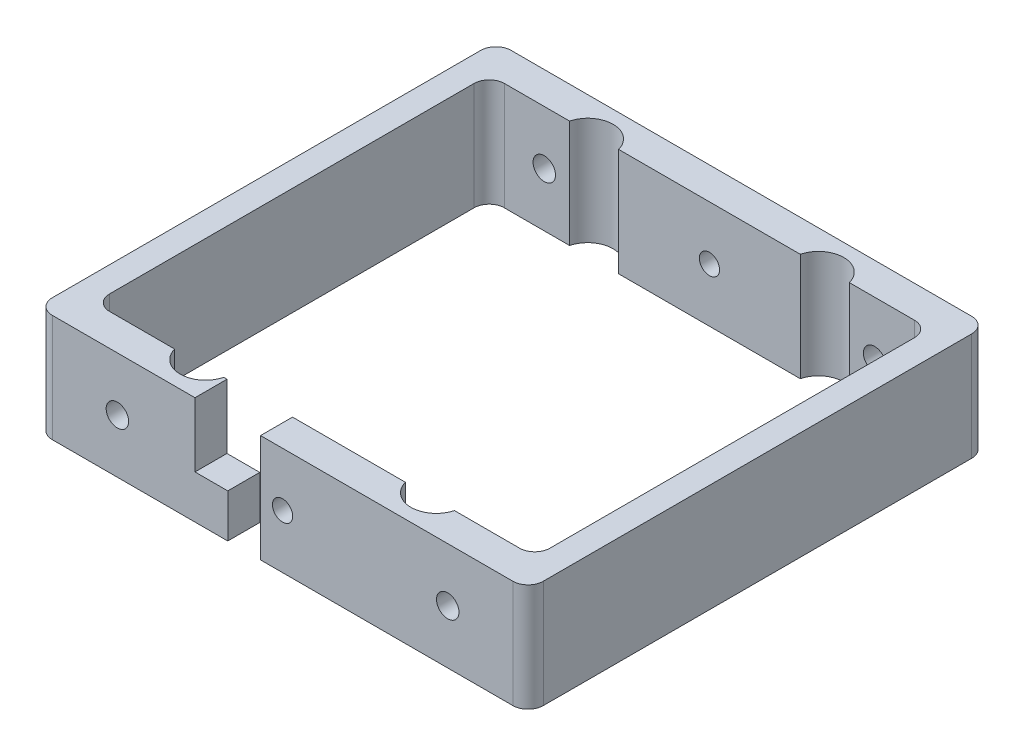
SolidWorks part; units mm, degrees
ref_plane "Front Plane" through (0, 0, 0) normal (0, 0, 1) x (1, 0, 0)
ref_plane "Top Plane" through (0, 0, 0) normal (0, 1, 0) x (1, 0, 0)
ref_plane "Right Plane" through (0, 0, 0) normal (1, 0, 0) x (0, 0, -1)
sketch "Sketch1" plane through (0, 0, 0) normal (0, 1, 0) x (1, 0, 0)
  line L1 (0, 0) -> (60, 0)
  line L2 (0, 0) -> (0, -6.32)
  line L3 (0, -6.32) -> (60, -6.32)
  line L4 (60, 0) -> (60, -6.32)
  dimension "D1" = 60
  dimension "D2" = 6.32
extrude "Boss-Extrude1" add sketch "Sketch1" along normal mid plane 21.28
sketch "Sketch2" plane through (0, 10.64, 0) normal (0, 1, 0) x (1, 0, 0)
  line L0 (0, 0) -> (0, -6.32) construction
  line L1 (0, -6.32) -> (60, -6.32) construction
  line L2 (60, -6.32) -> (60, 0) construction
  circle A0 centre (7.21, 1.25) radius 5
  circle A1 centre (52.79, 1.25) radius 5
  dimension "D1" = 7.21
  dimension "D3" = 7.21
  dimension "D2" = 7.57
  dimension "D4" = 7.57
extrude "Cut-Extrude1" cut sketch "Sketch2" against normal through all
sketch "Sketch3" plane through (60, 0, 0) normal (1, 0, 0) x (0, 0, -1)
  line L1 (-6.32, 10.64) -> (0, 10.64)
  line L2 (-6.32, 10.64) -> (-6.32, -10.64)
  line L3 (-6.32, -10.64) -> (0, -10.64)
  line L4 (0, 10.64) -> (0, -10.64)
extrude "Boss-Extrude2" add sketch "Sketch3" along normal blind 18.5
sketch "Sketch4" plane through (0, 0, 0) normal (-1, 0, 0) x (0, 0, 1)
  line L1 (0, 10.64) -> (6.32, 10.64)
  line L2 (0, 10.64) -> (0, -10.64)
  line L3 (0, -10.64) -> (6.32, -10.64)
  line L4 (6.32, 10.64) -> (6.32, -10.64)
extrude "Boss-Extrude3" add sketch "Sketch4" along normal blind 18.5
sketch "Sketch5" plane through (0, 0, 0) normal (0, 0, -1) x (-1, 0, 0)
  line L5 (-2.3688, -10.64) -> (18.5, -10.64) construction
  line L6 (18.5, 10.64) -> (13.5, 10.64)
  line L7 (18.5, 10.64) -> (18.5, -10.64)
  line L8 (18.5, -10.64) -> (13.5, -10.64)
  line L9 (13.5, 10.64) -> (13.5, -10.64)
  dimension "D1" = 5
extrude "Boss-Extrude6" add sketch "Sketch5" along normal blind 84.33
sketch "Sketch6" plane through (0, 0, 0) normal (0, 0, -1) x (-1, 0, 0)
  line L1 (-78.5, 10.64) -> (-73.5, 10.64)
  line L2 (-78.5, 10.64) -> (-78.5, -10.652)
  line L3 (-78.5, -10.652) -> (-73.5, -10.652)
  line L4 (-73.5, 10.64) -> (-73.5, -10.652)
  dimension "D1" = 5
extrude "Boss-Extrude7" add sketch "Sketch6" along normal blind 84.33
sketch "Sketch7" plane through (73.5, 0, 0) normal (-1, 0, 0) x (0, 0, 1)
  line L0 (-84.33, -10.652) -> (0, -10.652) construction
  line L1 (-84.33, 10.64) -> (-78.01, 10.64)
  line L2 (-84.33, 10.64) -> (-84.33, -10.652)
  line L3 (-84.33, -10.652) -> (-78.01, -10.652)
  line L4 (-78.01, 10.64) -> (-78.01, -10.652)
  dimension "D1" = 6.32
extrude "Boss-Extrude8" add sketch "Sketch7" along normal through all
sketch "Sketch9" plane through (0, 10.64, 0) normal (0, 1, 0) x (1, 0, 0)
  line L0 (-18.5, 84.33) -> (78.5, 84.33) construction
  circle A0 centre (7.21, 76.76) radius 5
  circle A1 centre (52.79, 76.76) radius 5
  dimension "D1" = 7.57
  dimension "D2" = 7.57
  dimension "D3" = 10
extrude "Cut-Extrude2" cut sketch "Sketch9" against normal through all
sketch "Sketch10" plane through (0, 0, -84.33) normal (0, 0, -1) x (-1, 0, 0)
  line L1 (-78.5, -10.64) -> (18.5, -10.64) construction
  line L2 (-30, -10.64) -> (-30, 10.64) construction
  line L3 (18.5, 10.64) -> (-78.5, 10.64) construction
  circle A0 centre (-62.6312, 0.005) radius 2.22
  circle A1 centre (2.6312, 0.005) radius 2.22
  dimension "D1" = 5
  dimension "D2" = 10.645
extrude "Cut-Extrude3" cut sketch "Sketch10" against normal through all
fillet "Fillet1" radius 3 8 edges at (-18.5, 0, 6.32) (78.5, 0, 6.32) (78.5, -0.006, -84.33) (-18.5, -0.006, -84.33) (-13.5, 0, -78.01) (-13.5, 0, 0) (73.5, -0.006, -78.01) (73.5, 0, 0)
sketch "Sketch13" plane through (0, 0, -84.33) normal (0, 0, -1) x (-1, 0, 0)
  line L1 (-75.5, 10.64) -> (-75.5, -10.652) construction
  line L2 (-75.5, -10.64) -> (15.5, -10.64) construction
  circle A0 centre (-30, 0.005) radius 2
  dimension "D1" = 45.5
  dimension "D2" = 10.645
extrude "Cut-Extrude4" cut sketch "Sketch13" against normal through all
sketch "Sketch16" plane through (0, -10.652, 0) normal (0, -1, 0) x (1, 0, 0)
  line L6 (75.5, -84.33) -> (-15.5, -84.33) construction
  line L7 (25.5729, -84.33) -> (12.6189, -84.33)
  line L8 (25.5729, -84.33) -> (25.5729, -78.01)
  line L9 (25.5729, -78.01) -> (12.6189, -78.01)
  line L10 (12.6189, -84.33) -> (12.6189, -78.01)
  line L11 (12.0512, -78.01) -> (47.9488, -78.01) construction
  dimension "D1" = 12.954
extrude "Cut-Extrude6" [suppressed] cut sketch "Sketch16" against normal mid plane 25.4
sketch "Sketch17" plane through (0, 10.64, 0) normal (0, 1, 0) x (1, 0, 0)
  line L1 (12.6964, 0.5862) -> (25.6504, 0.5862)
  line L2 (12.6964, 0.5862) -> (12.6964, -6.4457)
  line L3 (12.6964, -6.4457) -> (25.6504, -6.4457)
  line L4 (25.6504, 0.5862) -> (25.6504, -6.4457)
  point P4 (0, 0)
  dimension "D1" = 12.954
extrude "Cut-Extrude7" cut sketch "Sketch17" against normal mid plane 25.4
sketch "Sketch18" plane through (0, 0, 6.32) normal (0, 0, 1) x (1, 0, 0)
  line L0 (12.6964, -2.06) -> (25.6504, -2.06) construction
  line L1 (19.1734, -2.06) -> (25.6504, -2.06)
  line L2 (19.1734, -2.06) -> (19.1734, -10.64)
  line L3 (19.1734, -10.64) -> (25.6504, -10.64)
  line L4 (25.6504, -2.06) -> (25.6504, -10.64)
  line L5 (-15.5, -10.64) -> (75.5, -10.64) construction
extrude "Cut-Extrude8" cut sketch "Sketch18" against normal up to next
